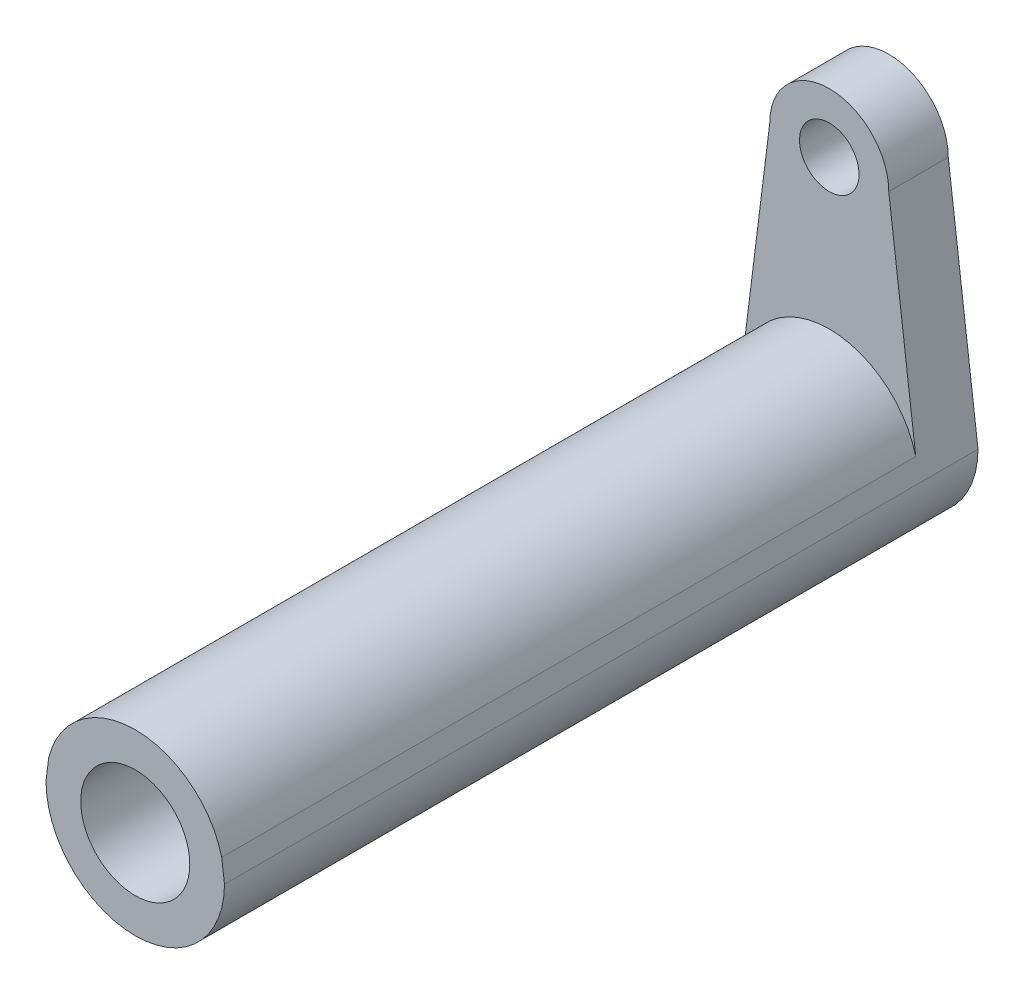
SolidWorks part; units mm, degrees
ref_plane "前视基准面" through (0, 0, 0) normal (0, 0, 1) x (1, 0, 0)
ref_plane "上视基准面" through (0, 0, 0) normal (0, 1, 0) x (1, 0, 0)
ref_plane "右视基准面" through (0, 0, 0) normal (1, 0, 0) x (0, 0, -1)
sketch "草图1" plane through (0, 0, 0) normal (0, 0, 1) x (1, 0, 0)
  line L0 (-1.8875, 2) -> (1.8875, 2)
  line L1 (0, -1000) -> (0, 49000) construction
  line L2 (-3, 12) -> (-4.5, 0)
  line L3 (3, 12) -> (4.5, 0)
  circle A0 centre (0, 0) radius 2.75
  circle A2 centre (0, 12) radius 1.5
  circle A3 centre (0, 0) radius 4.5
  circle A4 centre (0, 12) radius 3
  dimension "D1" = 5.5
  dimension "D3" = 12
  dimension "D4" = 3
  dimension "D5" = 9
  dimension "D6" = 6
  dimension "D2" = 2
extrude "凸台-拉伸3" add sketch "草图1" along normal blind 3 contours L1 A4 A2 | A4 L1 A2 | L1 A3 L3 A4 | A3 L1 A4 L2 | A3 L1 A0 L2 | L1 A3 L3 A0 | L1 L0 A0 | L0 L1 A0 region at (-0.7227, 2.3038, 0) region at (-2.6491, -1.0527, 0) region at (0.7227, 2.3038, 0) region at (0.1006, 3.625, 0) region at (-2.0968, 6.6121, 0) region at (2.0968, 6.6121, 0) region at (-2.0739, 9.9261, 0) region at (0.0671, 9.75, 0)
extrude "凸台-拉伸5" add sketch "草图1<12>" along normal blind 38 contours L1 L0 A0 | L0 L1 A0 | A3 L1 A0 L2 | L1 A3 L3 A0 region at (-0.7227, 2.3038, 0) region at (-2.6491, -1.0527, 0) region at (0.7227, 2.3038, 0) region at (0.1006, 3.625, 0)
sketch "草图1<12>" plane through (0, 0, 0) normal (0, 0, 1) x (1, 0, 0) same geometry as "草图1"
extrude "切除-拉伸1" cut sketch "草图1<16>" against normal blind 10 from surface contours L1 A0 L0 | L1 L0 A0 | A0 L1 L0 | L0 L1 A0 region at (-0.7227, 2.3038, 0) region at (-1.2068, -0.2055, 0) region at (0.7227, 2.3038, 0) region at (1.2068, -0.2055, 0) starting at face at (0, -0.375, 38)
sketch "草图1<16>" plane through (0, 0, 0) normal (0, 0, 1) x (1, 0, 0) same geometry as "草图1"
